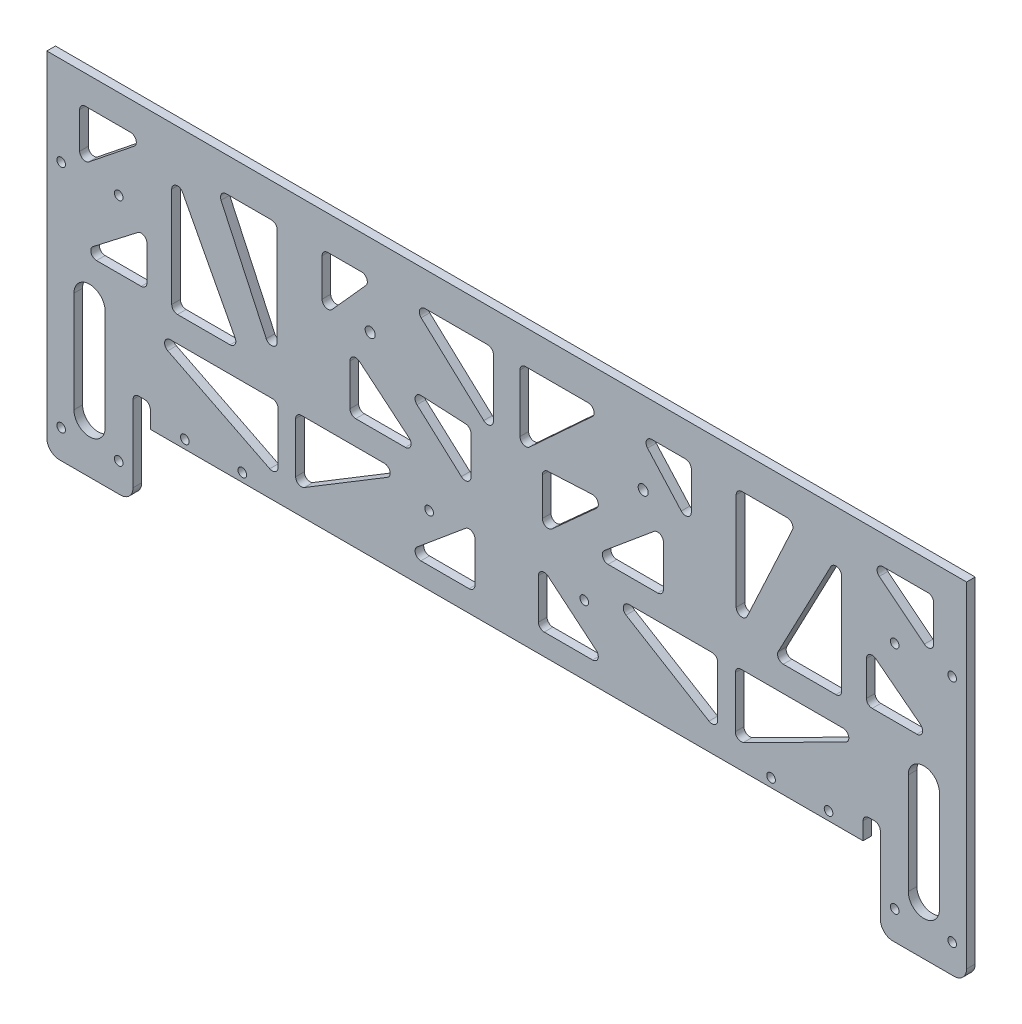
SolidWorks part; units mm, degrees
material "Thornel Mat VMA"
ref_plane "前视基准面" through (0, 0, 0) normal (0, 0, 1) x (1, 0, 0)
ref_plane "上视基准面" through (0, 0, 0) normal (0, 1, 0) x (1, 0, 0)
ref_plane "右视基准面" through (0, 0, 0) normal (1, 0, 0) x (0, 0, -1)
sketch "草图1" plane through (0, 0, 0) normal (0, 0, 1) x (1, 0, 0)
  line L1 (-160, 45.5) -> (160, 45.5)
  line L2 (-160, 45.5) -> (-160, -45.5)
  line L3 (-160, -45.5) -> (160, -45.5)
  line L4 (160, 45.5) -> (160, -45.5)
  line L5 (-160, 45.5) -> (160, -45.5) construction
  line L6 (-160, -45.5) -> (160, 45.5) construction
  point P0 (0, 0)
  dimension "D1" = 320
  dimension "D2" = 91
extrude "凸台-拉伸1" add sketch "草图1" along normal mid plane 3
sketch "草图2" plane through (0, 0, 1.5) normal (0, 0, 1) x (1, 0, 0)
  line L0 (0, 0) -> (0, -45.5) construction
  line L1 (-160, -45.5) -> (160, -45.5) construction
  line L2 (-160, -45.5) -> (-160, -50.5)
  line L3 (-160, -50.5) -> (160, -50.5)
  line L4 (160, -50.5) -> (160, -45.5)
  line L5 (160, -45.5) -> (-160, -45.5)
  line L6 (-130, -50.5) -> (-130, -42.5)
  line L7 (-130, -42.5) -> (-124, -42.5)
  line L8 (-124, -42.5) -> (-124, -50.5)
  line L9 (-160, 45.5) -> (-160, -45.5) construction
  line L10 (130, -42.5) -> (124, -42.5)
  line L11 (124, -42.5) -> (124, -50.5)
  line L12 (130, -50.5) -> (130, -42.5)
  line M12 (-160, -45.5) -> (160, -45.5)
  dimension "D1" = 5
  dimension "D2" = 6
  dimension "D3" = 30
  dimension "D4" = 8
extrude "凸台-拉伸3" add sketch "草图2" against normal blind 3 contours L3 L6 L2 M12 | L11 L5 L8 L3 M12 | L12 L3 L4 M12 region at (-145, -48, 1.5) region at (0, -48, 1.5) region at (145, -48, 1.5)
extrude "切除-拉伸1" cut sketch "草图2<4>" against normal blind 3 contours L8 L7 L6 L5 | L5 L12 L10 L11 region at (-127, -44, 1.5) region at (127, -44, 1.5)
sketch "草图2<4>" plane through (0, 0, 1.5) normal (0, 0, 1) x (1, 0, 0) same geometry as "草图2"
fillet "圆角1" radius 2 4 edges at (130, -42.5, 0) (124, -42.5, 0) (-124, -42.5, 0) (-130, -42.5, 0)
sketch "草图3" plane through (0, 0, 1.5) normal (0, 0, 1) x (1, 0, 0)
  circle A0 centre (-91.9859, -47.5) radius 1.5 construction
  circle A1 centre (-111.9859, -47.5) radius 1.5 construction
  circle A2 centre (-91.9859, -47.5) radius 1.5
  circle A3 centre (-111.9859, -47.5) radius 1.5
extrude "切除-拉伸2" cut sketch "草图3" against normal blind 10
mirror "镜向1" about plane through (0, 0, 0) normal (1, 0, 0) of "切除-拉伸2"
sketch "草图4" plane through (0, 0, 1.5) normal (0, 0, 1) x (1, 0, 0)
  circle A0 centre (-135, 14.5) radius 1.5 construction
  circle A1 centre (-155, 14.5) radius 1.5 construction
  circle A2 centre (-135, 14.5) radius 1.5
  circle A3 centre (-155, 14.5) radius 1.5
extrude "切除-拉伸3" cut sketch "草图4" against normal blind 10
mirror "镜向2" about plane through (0, 0, 0) normal (1, 0, 0) of "切除-拉伸3"
sketch "草图5" plane through (0, 0, -1.5) normal (0, 0, -1) x (-1, 0, 0)
  line L0 (130, -75.5) -> (160, -75.5) construction
  line L1 (160, -75.5) -> (160, 24.5) construction
  line L3 (130, 24.5) -> (130, -75.5) construction
  line L4 (-160, -75.5) -> (-130, -75.5) construction
  line L5 (-130, -75.5) -> (-130, 24.5) construction
  line L7 (-160, 24.5) -> (-160, -75.5) construction
  line L8 (134.3698, -75.5) -> (155.6302, -75.5)
  line L9 (160, -71.1302) -> (160, -50.5)
  line L11 (130, -50.5) -> (130, -71.1302)
  line L12 (-155.6302, -75.5) -> (-134.3698, -75.5)
  line L13 (-130, -71.1302) -> (-130, -50.5)
  line L15 (-160, -50.5) -> (-160, -71.1302)
  line L16 (-160, -50.5) -> (-130, -50.5)
  line L17 (160, -50.5) -> (130, -50.5)
  arc A0 (155.6302, -75.5) -> (160, -71.1302) centre (155.6302, -71.1302) ccw
  arc A1 (134.3698, -75.5) -> (130, -71.1302) centre (134.3698, -71.1302) cw
  arc A2 (-130, -71.1302) -> (-134.3698, -75.5) centre (-134.3698, -71.1302) cw
  arc A3 (-155.6302, -75.5) -> (-160, -71.1302) centre (-155.6302, -71.1302) cw
  dimension "D1" = 4.3698
extrude "凸台-拉伸5" add sketch "草图5" against normal up to surface (3 mm away) up to face at (133.5, 14.5, 1.5)
sketch "草图6" plane through (0, 0, -1.5) normal (0, 0, -1) x (-1, 0, 0)
  circle A0 centre (-155, -65.5) radius 1.5 construction
  circle A1 centre (-135, -65.5) radius 1.5 construction
  circle A2 centre (135, -65.5) radius 1.5 construction
  circle A3 centre (155, -65.5) radius 1.5 construction
  circle A4 centre (-155, -65.5) radius 1.5
  circle A5 centre (-135, -65.5) radius 1.5
  circle A6 centre (135, -65.5) radius 1.5
  circle A7 centre (155, -65.5) radius 1.5
extrude "切除-拉伸4" cut sketch "草图6" against normal blind 10
sketch "草图7" plane through (0, 0, -1.5) normal (0, 0, -1) x (-1, 0, 0)
  line L0 (0, -50.5) -> (0, -26.5) construction
  line L1 (124, -50.5) -> (-124, -50.5) construction
  line L2 (0, -26.5) -> (-27, -26.5) construction
  circle A0 centre (-27, -26.5) radius 1.5
  circle A1 centre (27, -26.5) radius 1.5
  dimension "D2" = 3
  dimension "D1" = 24
  dimension "D3" = 27
extrude "切除-拉伸5" cut sketch "草图7" against normal blind 10
sketch "草图8" plane through (0, 0, -1.5) normal (0, 0, -1) x (-1, 0, 0)
  arc A0 (47.5, 18.75) -> (47.5, 15.25) centre (47.5, 17) ccw construction
  arc A1 (47.5, 15.25) -> (47.5, 18.75) centre (47.5, 17) ccw construction
  arc A2 (-47.5, 15.25) -> (-47.5, 18.75) centre (-47.5, 17) ccw construction
  arc A3 (-47.5, 18.75) -> (-47.5, 15.25) centre (-47.5, 17) ccw construction
  arc A4 (47.5, 18.75) -> (47.5, 15.25) centre (47.5, 17) ccw
  arc A5 (47.5, 15.25) -> (47.5, 18.75) centre (47.5, 17) ccw
  arc A6 (-47.5, 15.25) -> (-47.5, 18.75) centre (-47.5, 17) ccw
  arc A7 (-47.5, 18.75) -> (-47.5, 15.25) centre (-47.5, 17) ccw
extrude "切除-拉伸6" cut sketch "草图8" against normal blind 6.47
sketch "草图9" plane through (0, 0, -1.5) normal (0, 0, -1) x (-1, 0, 0)
  line L0 (-146.5711, 35.5548) -> (-130.8717, 35.5548)
  line L1 (-129.6223, 31.993) -> (-145.3217, 19.4335)
  line L2 (-148.5711, 20.9953) -> (-148.5711, 33.5548)
  line L3 (-128.3936, 6.6026) -> (-143.939, -5.4191)
  line L4 (-142.7155, -9.0012) -> (-127.1701, -9.0012)
  line L5 (-125.1701, -7.0012) -> (-125.1701, 5.0205)
  line L6 (-116.5458, 25.5916) -> (-116.5458, -9.1624)
  line L7 (-114.5458, -11.1624) -> (-96.2464, -11.1624)
  line L8 (-94.4767, -8.2306) -> (-112.7761, 26.5234)
  line L9 (-117.9282, -23.8032) -> (-82.4445, -41.6092)
  line L10 (-79.5475, -39.8217) -> (-79.5475, -22.0156)
  line L11 (-81.5475, -20.0156) -> (-117.0312, -20.0156)
  line L12 (-97.5767, 33.6827) -> (-81.8526, 33.6827)
  line L13 (-79.8526, 31.6827) -> (-79.8526, -2.1821)
  line L14 (-83.6666, -3.0244) -> (-99.3907, 30.8404)
  line L15 (-145.1445, -22.7707) -> (-145.1445, -57.9112) construction
  line L16 (-139.7216, -22.7707) -> (-139.7216, -57.9112)
  line L17 (-150.5675, -22.7707) -> (-150.5675, -57.9112)
  line L18 (0, 0) -> (0, -50.5) construction
  line L19 (124, -50.5) -> (-124, -50.5) construction
  line L20 (-73.4259, -22.0156) -> (-73.4259, -39.5124)
  line L21 (-70.3894, -41.2228) -> (-41.5168, -23.7261)
  line L22 (-42.5533, -20.0156) -> (-71.4259, -20.0156)
  line L23 (-62.2277, 33.6827) -> (-50.4902, 33.6827)
  line L24 (-49.0007, 30.348) -> (-60.7382, 17.2493)
  line L25 (-64.2277, 18.584) -> (-64.2277, 31.6827)
  line L26 (-28.4117, 33.6827) -> (-6.6218, 33.6827)
  line L27 (-4.6218, 31.6827) -> (-4.6218, 11.628)
  line L28 (-7.9762, 10.1564) -> (-29.7661, 30.2111)
  line L29 (-51.2439, 6.361) -> (-33.9865, -8.0236)
  line L30 (-35.2671, -11.5598) -> (-52.5245, -11.5598)
  line L31 (-54.5245, -9.5598) -> (-54.5245, 4.8247)
  line L32 (-14.3352, -25.5059) -> (-31.1525, -39.5268)
  line L33 (-29.8718, -43.063) -> (-13.0544, -43.063)
  line L34 (-11.0544, -41.063) -> (-11.0544, -27.042)
  line L35 (-29.7781, 6.7875) -> (-14.3216, 6.0124)
  line L36 (-12.4218, 4.0149) -> (-12.4218, -9.1424)
  line L37 (-15.7608, -10.628) -> (-31.2174, 3.3045)
  line L38 (15.7608, -10.628) -> (31.2174, 3.3045)
  line L39 (12.4218, 4.0149) -> (12.4218, -9.1424)
  line L40 (29.7781, 6.7875) -> (14.3216, 6.0124)
  line L41 (11.0544, -41.063) -> (11.0544, -27.042)
  line L42 (29.8718, -43.063) -> (13.0544, -43.063)
  line L43 (14.3352, -25.5059) -> (31.1525, -39.5268)
  line L44 (54.5245, -9.5598) -> (54.5245, 4.8247)
  line L45 (35.2671, -11.5598) -> (52.5245, -11.5598)
  line L46 (51.2439, 6.361) -> (33.9865, -8.0236)
  line L47 (7.9762, 10.1564) -> (29.7661, 30.2111)
  line L48 (4.6218, 31.6827) -> (4.6218, 11.628)
  line L49 (28.4117, 33.6827) -> (6.6218, 33.6827)
  line L50 (64.2277, 18.584) -> (64.2277, 31.6827)
  line L51 (49.0007, 30.348) -> (60.7382, 17.2493)
  line L52 (62.2277, 33.6827) -> (50.4902, 33.6827)
  line L53 (42.5533, -20.0156) -> (71.4259, -20.0156)
  line L54 (70.3894, -41.2228) -> (41.5168, -23.7261)
  line L55 (73.4259, -22.0156) -> (73.4259, -39.5124)
  line L56 (83.6666, -3.0244) -> (99.3907, 30.8404)
  line L57 (79.8526, 31.6827) -> (79.8526, -2.1821)
  line L58 (97.5767, 33.6827) -> (81.8526, 33.6827)
  line L59 (81.5475, -20.0156) -> (117.0312, -20.0156)
  line L60 (79.5475, -39.8217) -> (79.5475, -22.0156)
  line L61 (117.9282, -23.8032) -> (82.4445, -41.6092)
  line L62 (94.4767, -8.2306) -> (112.7761, 26.5234)
  line L63 (114.5458, -11.1624) -> (96.2464, -11.1624)
  line L64 (116.5458, 25.5916) -> (116.5458, -9.1624)
  line L65 (125.1701, -7.0012) -> (125.1701, 5.0205)
  line L66 (142.7155, -9.0012) -> (127.1701, -9.0012)
  line L67 (128.3936, 6.6026) -> (143.939, -5.4191)
  line L68 (148.5711, 20.9953) -> (148.5711, 33.5548)
  line L69 (129.6223, 31.993) -> (145.3217, 19.4335)
  line L70 (146.5711, 35.5548) -> (130.8717, 35.5548)
  line L71 (145.1445, -22.7707) -> (145.1445, -57.9112) construction
  line L72 (139.7216, -22.7707) -> (139.7216, -57.9112)
  line L73 (150.5675, -22.7707) -> (150.5675, -57.9112)
  arc A0 (-139.7216, -22.7707) -> (-150.5675, -22.7707) centre (-145.1445, -22.7707) ccw
  arc A1 (-150.5675, -57.9112) -> (-139.7216, -57.9112) centre (-145.1445, -57.9112) ccw
  arc A2 (-13.0544, -43.063) -> (-11.0544, -41.063) centre (-13.0544, -41.063) ccw
  arc A3 (-29.8718, -43.063) -> (-31.1525, -39.5268) centre (-29.8718, -41.063) cw
  arc A4 (-11.0544, -27.042) -> (-14.3352, -25.5059) centre (-13.0544, -27.042) ccw
  arc A5 (-12.4218, -9.1424) -> (-15.7608, -10.628) centre (-14.4218, -9.1424) cw
  arc A6 (-12.4218, 4.0149) -> (-14.3216, 6.0124) centre (-14.4218, 4.0149) ccw
  arc A7 (-29.7781, 6.7875) -> (-31.2174, 3.3045) centre (-29.8783, 4.79) ccw
  arc A8 (-4.6218, 31.6827) -> (-6.6218, 33.6827) centre (-6.6218, 31.6827) ccw
  arc A9 (-29.7661, 30.2111) -> (-28.4117, 33.6827) centre (-28.4117, 31.6827) cw
  arc A10 (-7.9762, 10.1564) -> (-4.6218, 11.628) centre (-6.6218, 11.628) ccw
  arc A11 (-49.0007, 30.348) -> (-50.4902, 33.6827) centre (-50.4902, 31.6827) ccw
  arc A12 (-62.2277, 33.6827) -> (-64.2277, 31.6827) centre (-62.2277, 31.6827) ccw
  arc A13 (-64.2277, 18.584) -> (-60.7382, 17.2493) centre (-62.2277, 18.584) ccw
  arc A14 (-35.2671, -11.5598) -> (-33.9865, -8.0236) centre (-35.2671, -9.5598) ccw
  arc A15 (-51.2439, 6.361) -> (-54.5245, 4.8247) centre (-52.5245, 4.8247) ccw
  arc A16 (-52.5245, -11.5598) -> (-54.5245, -9.5598) centre (-52.5245, -9.5598) cw
  arc A17 (-42.5533, -20.0156) -> (-41.5168, -23.7261) centre (-42.5533, -22.0156) cw
  arc A18 (-71.4259, -20.0156) -> (-73.4259, -22.0156) centre (-71.4259, -22.0156) ccw
  arc A19 (-70.3894, -41.2228) -> (-73.4259, -39.5124) centre (-71.4259, -39.5124) cw
  arc A20 (-79.5475, -39.8217) -> (-82.4445, -41.6092) centre (-81.5475, -39.8217) cw
  arc A21 (-79.5475, -22.0156) -> (-81.5475, -20.0156) centre (-81.5475, -22.0156) ccw
  arc A22 (-117.0312, -20.0156) -> (-117.9282, -23.8032) centre (-117.0312, -22.0156) ccw
  arc A23 (-79.8526, 31.6827) -> (-81.8526, 33.6827) centre (-81.8526, 31.6827) ccw
  arc A24 (-99.3907, 30.8404) -> (-97.5767, 33.6827) centre (-97.5767, 31.6827) cw
  arc A25 (-79.8526, -2.1821) -> (-83.6666, -3.0244) centre (-81.8526, -2.1821) cw
  arc A26 (-96.2464, -11.1624) -> (-94.4767, -8.2306) centre (-96.2464, -9.1624) ccw
  arc A27 (-114.5458, -11.1624) -> (-116.5458, -9.1624) centre (-114.5458, -9.1624) cw
  arc A28 (-112.7761, 26.5234) -> (-116.5458, 25.5916) centre (-114.5458, 25.5916) ccw
  arc A29 (-125.1701, 5.0205) -> (-128.3936, 6.6026) centre (-127.1701, 5.0205) ccw
  arc A30 (-125.1701, -7.0012) -> (-127.1701, -9.0012) centre (-127.1701, -7.0012) cw
  arc A31 (-142.7155, -9.0012) -> (-143.939, -5.4191) centre (-142.7155, -7.0012) cw
  arc A32 (-129.6223, 31.993) -> (-130.8717, 35.5548) centre (-130.8717, 33.5548) ccw
  arc A33 (-146.5711, 35.5548) -> (-148.5711, 33.5548) centre (-146.5711, 33.5548) ccw
  arc A34 (-145.3217, 19.4335) -> (-148.5711, 20.9953) centre (-146.5711, 20.9953) cw
  arc A35 (145.3217, 19.4335) -> (148.5711, 20.9953) centre (146.5711, 20.9953) ccw
  arc A36 (146.5711, 35.5548) -> (148.5711, 33.5548) centre (146.5711, 33.5548) cw
  arc A37 (129.6223, 31.993) -> (130.8717, 35.5548) centre (130.8717, 33.5548) cw
  arc A38 (142.7155, -9.0012) -> (143.939, -5.4191) centre (142.7155, -7.0012) ccw
  arc A39 (125.1701, -7.0012) -> (127.1701, -9.0012) centre (127.1701, -7.0012) ccw
  arc A40 (125.1701, 5.0205) -> (128.3936, 6.6026) centre (127.1701, 5.0205) cw
  arc A41 (112.7761, 26.5234) -> (116.5458, 25.5916) centre (114.5458, 25.5916) cw
  arc A42 (114.5458, -11.1624) -> (116.5458, -9.1624) centre (114.5458, -9.1624) ccw
  arc A43 (96.2464, -11.1624) -> (94.4767, -8.2306) centre (96.2464, -9.1624) cw
  arc A44 (79.8526, -2.1821) -> (83.6666, -3.0244) centre (81.8526, -2.1821) ccw
  arc A45 (99.3907, 30.8404) -> (97.5767, 33.6827) centre (97.5767, 31.6827) ccw
  arc A46 (79.8526, 31.6827) -> (81.8526, 33.6827) centre (81.8526, 31.6827) cw
  arc A47 (117.0312, -20.0156) -> (117.9282, -23.8032) centre (117.0312, -22.0156) cw
  arc A48 (79.5475, -22.0156) -> (81.5475, -20.0156) centre (81.5475, -22.0156) cw
  arc A49 (79.5475, -39.8217) -> (82.4445, -41.6092) centre (81.5475, -39.8217) ccw
  arc A50 (70.3894, -41.2228) -> (73.4259, -39.5124) centre (71.4259, -39.5124) ccw
  arc A51 (71.4259, -20.0156) -> (73.4259, -22.0156) centre (71.4259, -22.0156) cw
  arc A52 (42.5533, -20.0156) -> (41.5168, -23.7261) centre (42.5533, -22.0156) ccw
  arc A53 (52.5245, -11.5598) -> (54.5245, -9.5598) centre (52.5245, -9.5598) ccw
  arc A54 (51.2439, 6.361) -> (54.5245, 4.8247) centre (52.5245, 4.8247) cw
  arc A55 (35.2671, -11.5598) -> (33.9865, -8.0236) centre (35.2671, -9.5598) cw
  arc A56 (64.2277, 18.584) -> (60.7382, 17.2493) centre (62.2277, 18.584) cw
  arc A57 (62.2277, 33.6827) -> (64.2277, 31.6827) centre (62.2277, 31.6827) cw
  arc A58 (49.0007, 30.348) -> (50.4902, 33.6827) centre (50.4902, 31.6827) cw
  arc A59 (7.9762, 10.1564) -> (4.6218, 11.628) centre (6.6218, 11.628) cw
  arc A60 (29.7661, 30.2111) -> (28.4117, 33.6827) centre (28.4117, 31.6827) ccw
  arc A61 (4.6218, 31.6827) -> (6.6218, 33.6827) centre (6.6218, 31.6827) cw
  arc A62 (29.7781, 6.7875) -> (31.2174, 3.3045) centre (29.8783, 4.79) cw
  arc A63 (12.4218, 4.0149) -> (14.3216, 6.0124) centre (14.4218, 4.0149) cw
  arc A64 (12.4218, -9.1424) -> (15.7608, -10.628) centre (14.4218, -9.1424) ccw
  arc A65 (11.0544, -27.042) -> (14.3352, -25.5059) centre (13.0544, -27.042) cw
  arc A66 (29.8718, -43.063) -> (31.1525, -39.5268) centre (29.8718, -41.063) ccw
  arc A67 (13.0544, -43.063) -> (11.0544, -41.063) centre (13.0544, -41.063) cw
  arc A68 (139.7216, -22.7707) -> (150.5675, -22.7707) centre (145.1445, -22.7707) cw
  arc A69 (150.5675, -57.9112) -> (139.7216, -57.9112) centre (145.1445, -57.9112) cw
  point P17 (-145.1445, -40.3409)
  point P65 (-46.0125, 33.6827)
  point P90 (-79.8526, 33.6827)
  point P101 (-116.5458, 33.6827)
  point P213 (116.5458, 33.6827)
  point P214 (79.8526, 33.6827)
  point P215 (46.0125, 33.6827)
  point P218 (145.1445, -40.3409)
  dimension "D1" = 2
extrude "切除-拉伸7" cut sketch "草图9" against normal blind 10
